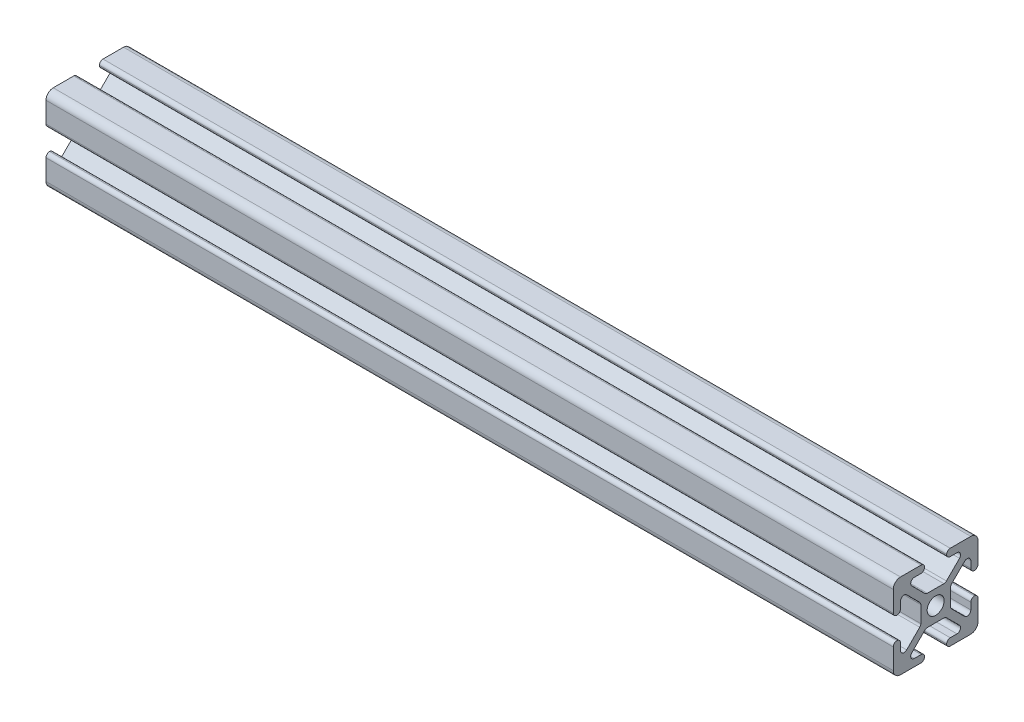
SolidWorks part; units mm, degrees
ref_plane "Front Plane" through (0, 0, 0) normal (1, 0, 0) x (0, 1, 0)
ref_plane "Top Plane" through (0, 0, 0) normal (0, 0, 1) x (0, 1, 0)
ref_plane "Right Plane" through (0, 0, 0) normal (0, 1, 0) x (-1, 0, 0)
sketch "Sketch1" plane through (0, 0, 0) normal (1, 0, 0) x (0, 1, 0)
  line L0 (0, 0) -> (0, 12.5) construction
  line L1 (-12.5, -12.5) -> (12.5, -12.5)
  line L2 (-12.5, -12.5) -> (-12.5, 12.5)
  line L3 (-12.5, 12.5) -> (12.5, 12.5)
  line L4 (12.5, -12.5) -> (12.5, 12.5)
  line L5 (-12.5, -12.5) -> (12.5, 12.5) construction
  line L6 (-12.5, 12.5) -> (12.5, -12.5) construction
  line L7 (-3.25, 12.5) -> (-3.25, 10.37)
  line L8 (-3.25, 10.37) -> (-8.8639, 10.37)
  line L9 (-8.8639, 10.37) -> (-2.8739, 4.38)
  line L10 (-2.8739, 4.38) -> (2.8739, 4.38)
  line L11 (8.8639, 10.37) -> (2.8739, 4.38)
  line L12 (3.25, 10.37) -> (8.8639, 10.37)
  line L13 (3.25, 12.5) -> (3.25, 10.37)
  line L14 (12.5, -3.25) -> (10.37, -3.25)
  line L15 (10.37, -3.25) -> (10.37, -8.8639)
  line L16 (10.37, -8.8639) -> (4.38, -2.8739)
  line L17 (4.38, 2.8739) -> (4.38, -2.8739)
  line L18 (10.37, 8.8639) -> (4.38, 2.8739)
  line L19 (10.37, 3.25) -> (10.37, 8.8639)
  line L20 (12.5, 3.25) -> (10.37, 3.25)
  line L21 (-3.25, -12.5) -> (-3.25, -10.37)
  line L22 (-3.25, -10.37) -> (-8.8639, -10.37)
  line L23 (-8.8639, -10.37) -> (-2.8739, -4.38)
  line L24 (2.8739, -4.38) -> (-2.8739, -4.38)
  line L25 (8.8639, -10.37) -> (2.8739, -4.38)
  line L26 (3.25, -10.37) -> (8.8639, -10.37)
  line L27 (3.25, -12.5) -> (3.25, -10.37)
  line L28 (-12.5, 3.25) -> (-10.37, 3.25)
  line L29 (-10.37, 3.25) -> (-10.37, 8.8639)
  line L30 (-10.37, 8.8639) -> (-4.38, 2.8739)
  line L31 (-4.38, -2.8739) -> (-4.38, 2.8739)
  line L32 (-10.37, -8.8639) -> (-4.38, -2.8739)
  line L33 (-10.37, -3.25) -> (-10.37, -8.8639)
  line L34 (-12.5, -3.25) -> (-10.37, -3.25)
  circle A0 centre (0, 0) radius 2.5
  point P0 (0, 0)
  point P15 (0, 4.38)
  dimension "D3" = 5
  dimension "D1" = 25
  dimension "D2" = 25
  dimension "D4" = 2.13
  dimension "D5" = 2.13
  dimension "D6" = 6.5
  dimension "D7" = 4.38
  dimension "D8" = 4
extrude "Boss-Extrude1" add sketch "Sketch1" along normal blind 250 contours L34 L2 L1 L21 L22 L23 L24 L25 L26 L27 L4 L14 L15 L16 L17 L18 L19 L20 L3 L13 L12 L11 L10 L9 L8 L7 L28 L29 L30 L31 L32 L33 A0 region at (0, -12.1464, -7.875)
fillet "Fillet1" radius 1.065 32 edges at (125, -10.37, -8.8639) (125, 2.8739, -4.38) (125, -2.8739, -4.38) (125, -4.38, 2.8739) (125, -4.38, -2.8739) (125, -2.8739, 4.38) (125, 2.8739, 4.38) (125, 4.38, 2.8739) (125, 4.38, -2.8739) (125, -8.8639, -10.37) (125, 8.8639, -10.37) (125, 10.37, -8.8639) (125, -10.37, 8.8639) (125, -8.8639, 10.37) (125, 10.37, 8.8639) (125, 8.8639, 10.37) (125, 12.5, 3.25) (125, -3.25, -12.5) (125, -10.37, 3.25) (125, 10.37, 3.25) (125, -10.37, -3.25) (125, -12.5, -3.25) (125, -12.5, 3.25) (125, 3.25, -10.37) (125, -3.25, -10.37) (125, 3.25, -12.5) (125, 10.37, -3.25) (125, 12.5, -3.25) (125, 3.25, 12.5) (125, 3.25, 10.37) (125, -3.25, 10.37) (125, -3.25, 12.5)
fillet "Fillet2" radius 2.13 4 edges at (125, 12.5, -12.5) (125, -12.5, -12.5) (125, 12.5, 12.5) (125, -12.5, 12.5)
sketch "Sketch2" plane through (250, 0, 0) normal (1, 0, 0) x (0, 1, 0)
  line L0 (10.37, -12.5) -> (4.315, -12.5)
  line L1 (10.37, -12.5) -> (4.315, -12.5)
  line L2 (4.315, -10.37) -> (6.2927, -10.37)
  line L3 (4.315, -10.37) -> (6.2927, -10.37)
  line L4 (7.0458, -8.5519) -> (3.1858, -4.6919)
  line L5 (7.0458, -8.5519) -> (3.1858, -4.6919)
  line L6 (2.4327, -4.38) -> (-2.4327, -4.38)
  line L7 (2.4327, -4.38) -> (-2.4327, -4.38)
  line L8 (-3.1858, -4.6919) -> (-7.0458, -8.5519)
  line L9 (-3.1858, -4.6919) -> (-7.0458, -8.5519)
  line L10 (-6.2927, -10.37) -> (-4.315, -10.37)
  line L11 (-6.2927, -10.37) -> (-4.315, -10.37)
  line L12 (-4.315, -12.5) -> (-10.37, -12.5)
  line L13 (-4.315, -12.5) -> (-10.37, -12.5)
  line L14 (-12.5, -10.37) -> (-12.5, -4.315)
  line L15 (-12.5, -10.37) -> (-12.5, -4.315)
  line L16 (-10.37, -4.315) -> (-10.37, -6.2927)
  line L17 (-10.37, -4.315) -> (-10.37, -6.2927)
  line L18 (-8.5519, -7.0458) -> (-4.6919, -3.1858)
  line L19 (-8.5519, -7.0458) -> (-4.6919, -3.1858)
  line L20 (-4.38, -2.4327) -> (-4.38, 2.4327)
  line L21 (-4.38, -2.4327) -> (-4.38, 2.4327)
  line L22 (-4.6919, 3.1858) -> (-8.5519, 7.0458)
  line L23 (-4.6919, 3.1858) -> (-8.5519, 7.0458)
  line L24 (-10.37, 6.2927) -> (-10.37, 4.315)
  line L25 (-10.37, 6.2927) -> (-10.37, 4.315)
  line L26 (-12.5, 4.315) -> (-12.5, 10.37)
  line L27 (-12.5, 4.315) -> (-12.5, 10.37)
  line L28 (-10.37, 12.5) -> (-4.315, 12.5)
  line L29 (-10.37, 12.5) -> (-4.315, 12.5)
  line L30 (-4.315, 10.37) -> (-6.2927, 10.37)
  line L31 (-4.315, 10.37) -> (-6.2927, 10.37)
  line L32 (-7.0458, 8.5519) -> (-3.1858, 4.6919)
  line L33 (-7.0458, 8.5519) -> (-3.1858, 4.6919)
  line L34 (-2.4327, 4.38) -> (2.4327, 4.38)
  line L35 (-2.4327, 4.38) -> (2.4327, 4.38)
  line L36 (3.1858, 4.6919) -> (7.0458, 8.5519)
  line L37 (3.1858, 4.6919) -> (7.0458, 8.5519)
  line L38 (6.2927, 10.37) -> (4.315, 10.37)
  line L39 (6.2927, 10.37) -> (4.315, 10.37)
  line L40 (4.315, 12.5) -> (10.37, 12.5)
  line L41 (4.315, 12.5) -> (10.37, 12.5)
  line L42 (12.5, 10.37) -> (12.5, 4.315)
  line L43 (12.5, 10.37) -> (12.5, 4.315)
  line L44 (10.37, 4.315) -> (10.37, 6.2927)
  line L45 (10.37, 4.315) -> (10.37, 6.2927)
  line L46 (8.5519, 7.0458) -> (4.6919, 3.1858)
  line L47 (8.5519, 7.0458) -> (4.6919, 3.1858)
  line L48 (4.38, 2.4327) -> (4.38, -2.4327)
  line L49 (4.38, 2.4327) -> (4.38, -2.4327)
  line L50 (4.6919, -3.1858) -> (8.5519, -7.0458)
  line L51 (4.6919, -3.1858) -> (8.5519, -7.0458)
  line L52 (10.37, -6.2927) -> (10.37, -4.315)
  line L53 (10.37, -6.2927) -> (10.37, -4.315)
  line L54 (12.5, -4.315) -> (12.5, -10.37)
  line L55 (12.5, -4.315) -> (12.5, -10.37)
  arc A0 (10.37, -12.5) -> (12.5, -10.37) centre (10.37, -10.37) ccw
  circle A1 centre (0, 0) radius 2.5
  circle A2 centre (0, 0) radius 2.5
  arc A3 (10.37, -12.5) -> (12.5, -10.37) centre (10.37, -10.37) ccw
  arc A4 (3.25, -11.435) -> (4.315, -12.5) centre (4.315, -11.435) ccw
  arc A5 (3.25, -11.435) -> (4.315, -12.5) centre (4.315, -11.435) ccw
  arc A6 (4.315, -10.37) -> (3.25, -11.435) centre (4.315, -11.435) ccw
  arc A7 (4.315, -10.37) -> (3.25, -11.435) centre (4.315, -11.435) ccw
  arc A8 (6.2927, -10.37) -> (7.0458, -8.5519) centre (6.2927, -9.305) ccw
  arc A9 (6.2927, -10.37) -> (7.0458, -8.5519) centre (6.2927, -9.305) ccw
  arc A10 (3.1858, -4.6919) -> (2.4327, -4.38) centre (2.4327, -5.445) ccw
  arc A11 (3.1858, -4.6919) -> (2.4327, -4.38) centre (2.4327, -5.445) ccw
  arc A12 (-2.4327, -4.38) -> (-3.1858, -4.6919) centre (-2.4327, -5.445) ccw
  arc A13 (-2.4327, -4.38) -> (-3.1858, -4.6919) centre (-2.4327, -5.445) ccw
  arc A14 (-7.0458, -8.5519) -> (-6.2927, -10.37) centre (-6.2927, -9.305) ccw
  arc A15 (-7.0458, -8.5519) -> (-6.2927, -10.37) centre (-6.2927, -9.305) ccw
  arc A16 (-3.25, -11.435) -> (-4.315, -10.37) centre (-4.315, -11.435) ccw
  arc A17 (-3.25, -11.435) -> (-4.315, -10.37) centre (-4.315, -11.435) ccw
  arc A18 (-4.315, -12.5) -> (-3.25, -11.435) centre (-4.315, -11.435) ccw
  arc A19 (-4.315, -12.5) -> (-3.25, -11.435) centre (-4.315, -11.435) ccw
  arc A20 (-12.5, -10.37) -> (-10.37, -12.5) centre (-10.37, -10.37) ccw
  arc A21 (-12.5, -10.37) -> (-10.37, -12.5) centre (-10.37, -10.37) ccw
  arc A22 (-11.435, -3.25) -> (-12.5, -4.315) centre (-11.435, -4.315) ccw
  arc A23 (-11.435, -3.25) -> (-12.5, -4.315) centre (-11.435, -4.315) ccw
  arc A24 (-10.37, -4.315) -> (-11.435, -3.25) centre (-11.435, -4.315) ccw
  arc A25 (-10.37, -4.315) -> (-11.435, -3.25) centre (-11.435, -4.315) ccw
  arc A26 (-10.37, -6.2927) -> (-8.5519, -7.0458) centre (-9.305, -6.2927) ccw
  arc A27 (-10.37, -6.2927) -> (-8.5519, -7.0458) centre (-9.305, -6.2927) ccw
  arc A28 (-4.6919, -3.1858) -> (-4.38, -2.4327) centre (-5.445, -2.4327) ccw
  arc A29 (-4.6919, -3.1858) -> (-4.38, -2.4327) centre (-5.445, -2.4327) ccw
  arc A30 (-4.38, 2.4327) -> (-4.6919, 3.1858) centre (-5.445, 2.4327) ccw
  arc A31 (-4.38, 2.4327) -> (-4.6919, 3.1858) centre (-5.445, 2.4327) ccw
  arc A32 (-8.5519, 7.0458) -> (-10.37, 6.2927) centre (-9.305, 6.2927) ccw
  arc A33 (-8.5519, 7.0458) -> (-10.37, 6.2927) centre (-9.305, 6.2927) ccw
  arc A34 (-11.435, 3.25) -> (-10.37, 4.315) centre (-11.435, 4.315) ccw
  arc A35 (-11.435, 3.25) -> (-10.37, 4.315) centre (-11.435, 4.315) ccw
  arc A36 (-12.5, 4.315) -> (-11.435, 3.25) centre (-11.435, 4.315) ccw
  arc A37 (-12.5, 4.315) -> (-11.435, 3.25) centre (-11.435, 4.315) ccw
  arc A38 (-10.37, 12.5) -> (-12.5, 10.37) centre (-10.37, 10.37) ccw
  arc A39 (-10.37, 12.5) -> (-12.5, 10.37) centre (-10.37, 10.37) ccw
  arc A40 (-3.25, 11.435) -> (-4.315, 12.5) centre (-4.315, 11.435) ccw
  arc A41 (-3.25, 11.435) -> (-4.315, 12.5) centre (-4.315, 11.435) ccw
  arc A42 (-4.315, 10.37) -> (-3.25, 11.435) centre (-4.315, 11.435) ccw
  arc A43 (-4.315, 10.37) -> (-3.25, 11.435) centre (-4.315, 11.435) ccw
  arc A44 (-6.2927, 10.37) -> (-7.0458, 8.5519) centre (-6.2927, 9.305) ccw
  arc A45 (-6.2927, 10.37) -> (-7.0458, 8.5519) centre (-6.2927, 9.305) ccw
  arc A46 (-3.1858, 4.6919) -> (-2.4327, 4.38) centre (-2.4327, 5.445) ccw
  arc A47 (-3.1858, 4.6919) -> (-2.4327, 4.38) centre (-2.4327, 5.445) ccw
  arc A48 (2.4327, 4.38) -> (3.1858, 4.6919) centre (2.4327, 5.445) ccw
  arc A49 (2.4327, 4.38) -> (3.1858, 4.6919) centre (2.4327, 5.445) ccw
  arc A50 (7.0458, 8.5519) -> (6.2927, 10.37) centre (6.2927, 9.305) ccw
  arc A51 (7.0458, 8.5519) -> (6.2927, 10.37) centre (6.2927, 9.305) ccw
  arc A52 (3.25, 11.435) -> (4.315, 10.37) centre (4.315, 11.435) ccw
  arc A53 (3.25, 11.435) -> (4.315, 10.37) centre (4.315, 11.435) ccw
  arc A54 (4.315, 12.5) -> (3.25, 11.435) centre (4.315, 11.435) ccw
  arc A55 (4.315, 12.5) -> (3.25, 11.435) centre (4.315, 11.435) ccw
  arc A56 (12.5, 10.37) -> (10.37, 12.5) centre (10.37, 10.37) ccw
  arc A57 (12.5, 10.37) -> (10.37, 12.5) centre (10.37, 10.37) ccw
  arc A58 (11.435, 3.25) -> (12.5, 4.315) centre (11.435, 4.315) ccw
  arc A59 (11.435, 3.25) -> (12.5, 4.315) centre (11.435, 4.315) ccw
  arc A60 (10.37, 4.315) -> (11.435, 3.25) centre (11.435, 4.315) ccw
  arc A61 (10.37, 4.315) -> (11.435, 3.25) centre (11.435, 4.315) ccw
  arc A62 (10.37, 6.2927) -> (8.5519, 7.0458) centre (9.305, 6.2927) ccw
  arc A63 (10.37, 6.2927) -> (8.5519, 7.0458) centre (9.305, 6.2927) ccw
  arc A64 (4.6919, 3.1858) -> (4.38, 2.4327) centre (5.445, 2.4327) ccw
  arc A65 (4.6919, 3.1858) -> (4.38, 2.4327) centre (5.445, 2.4327) ccw
  arc A66 (4.38, -2.4327) -> (4.6919, -3.1858) centre (5.445, -2.4327) ccw
  arc A67 (4.38, -2.4327) -> (4.6919, -3.1858) centre (5.445, -2.4327) ccw
  arc A68 (8.5519, -7.0458) -> (10.37, -6.2927) centre (9.305, -6.2927) ccw
  arc A69 (8.5519, -7.0458) -> (10.37, -6.2927) centre (9.305, -6.2927) ccw
  arc A70 (11.435, -3.25) -> (10.37, -4.315) centre (11.435, -4.315) ccw
  arc A71 (11.435, -3.25) -> (10.37, -4.315) centre (11.435, -4.315) ccw
  arc A72 (12.5, -4.315) -> (11.435, -3.25) centre (11.435, -4.315) ccw
  arc A73 (12.5, -4.315) -> (11.435, -3.25) centre (11.435, -4.315) ccw
  dimension "D1" = 0
